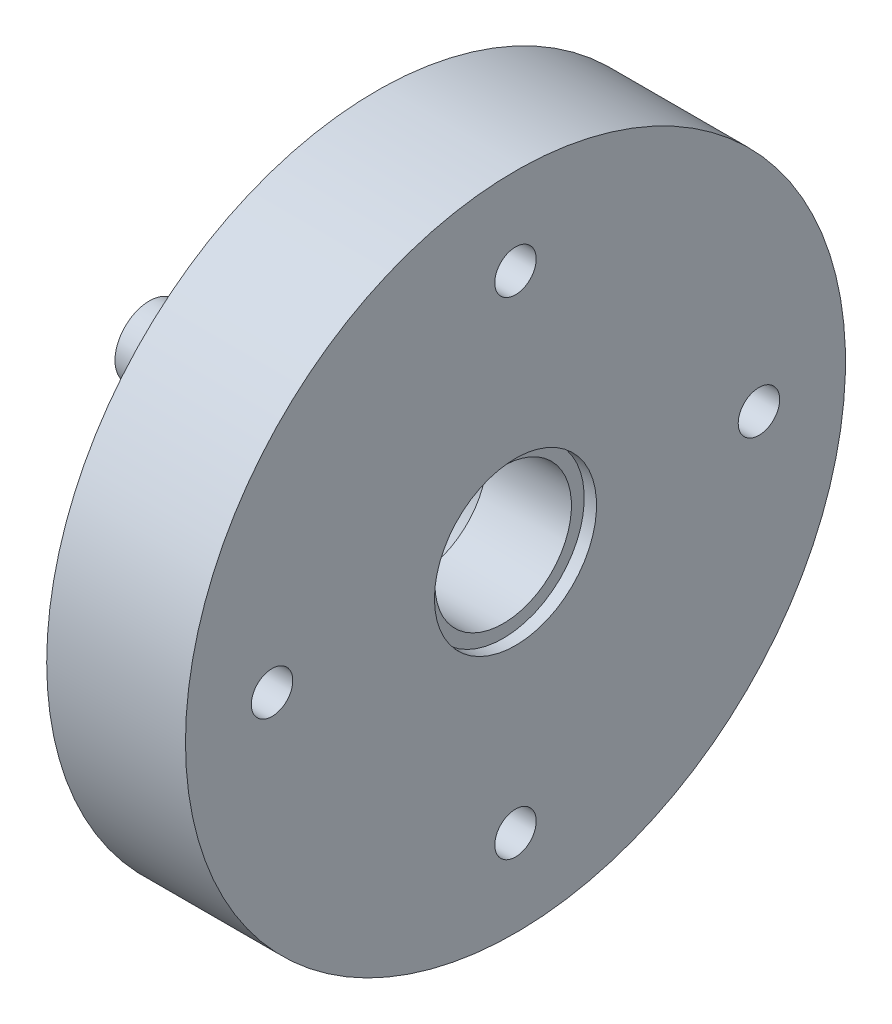
SolidWorks part; units mm, degrees
ref_plane "Front Plane" through (0, 0, 0) normal (0, 0, 1) x (1, 0, 0)
ref_plane "Top Plane" through (0, 0, 0) normal (0, 1, 0) x (1, 0, 0)
ref_plane "Right Plane" through (0, 0, 0) normal (1, 0, 0) x (0, 0, -1)
sketch "Sketch1" plane through (0, 0, 0) normal (0, 0, 1) x (1, 0, 0)
  line L0 (-795.1638, 11.7142) -> (36114.285, 11.7142) construction
  line L3 (-71.2919, 14.8842) -> (-71.2919, 14.5342)
  line L8 (-75.7419, 13.3992) -> (-59.4889, 13.3992)
  line L9 (-75.7419, 13.3992) -> (-75.7419, 14.5342)
  line L10 (-45.7058, 19.9775) -> (-45.7058, 38.788)
  line L12 (-45.7058, 38.788) -> (-57.0912, 38.788)
  line L13 (-62.3716, 14.5342) -> (-59.4889, 23.788)
  line L15 (-45.7058, 19.9775) -> (-45.7058, 18.3642)
  line L16 (-45.7058, 18.3642) -> (-46.7158, 18.3642)
  line L17 (-46.7158, 18.3642) -> (-46.7158, 17.3142)
  line L18 (-57.0912, 38.788) -> (-57.0912, 23.788)
  line L19 (-59.4889, 23.788) -> (-57.0912, 23.788)
  line L20 (-59.4889, 13.3992) -> (-53.6375, 17.3142)
  line L21 (-75.7419, 14.5342) -> (-71.2919, 14.8842)
  line L22 (-53.6375, 17.3142) -> (-46.7158, 17.3142)
  line L23 (-71.2919, 14.5342) -> (-66.8419, 14.8842)
  line L26 (-66.8419, 14.8842) -> (-66.8419, 14.5342)
  line L27 (-66.8419, 14.5342) -> (-62.3716, 14.8842)
  line L28 (-62.3716, 14.8842) -> (-62.3716, 14.5342)
  dimension "D1" = 13.3
  dimension "D5" = 11.2
  dimension "D2" = 6.34
  dimension "D3" = 1.01
  dimension "D4" = 15
  dimension "D6" = 3.37
  dimension "D7" = 5.64
revolve "Revolve17" add sketch "Sketch1" angle 360 about L0
sketch "Sketch3" plane through (-57.0912, 0, 0) normal (-1, 0, 0) x (0, 0, 1)
  circle A2 centre (0, 11.7142) radius 19.9711 construction
  point P2 (0, 31.6853)
  point P3 (19.9711, 11.7142)
  point P4 (0, -8.2569)
  point P6 (-19.9711, 11.7142)
hole_wizard "CBORE for M3 Hex Socket Head Cap Screw1" positions "Sketch3" profile "Sketch4" counterbore size "M3" standard "ISO" end condition through all
sketch "Sketch4" plane through (-57.0912, 11.7142, -19.9711) normal (0, 1, 0) x (0, 0, 1)
  line L0 (0, 0) -> (0, 11.3854)
  line L1 (0, 11.3854) -> (1.7, 11.3854)
  line L3 (1.7, 11.3854) -> (1.7, 3.4)
  line L4 (1.675, 3.4) -> (1.7, 3.4)
  line L5 (1.675, 3.4) -> (1.675, 0.025)
  line L6 (1.675, 0.025) -> (1.7, 0)
  line L7 (1.7, 0) -> (0, 0)
  line L8 (-1.675, 0.025) -> (-1.7, 0) construction
  line L11 (0, -6.35) -> (0, 107.95) construction
  dimension "Thru Hole Dia." = 3.4
  dimension "Thru Hole Depth" = 11.3854
  dimension "Near C'Sink Angle" = 90
